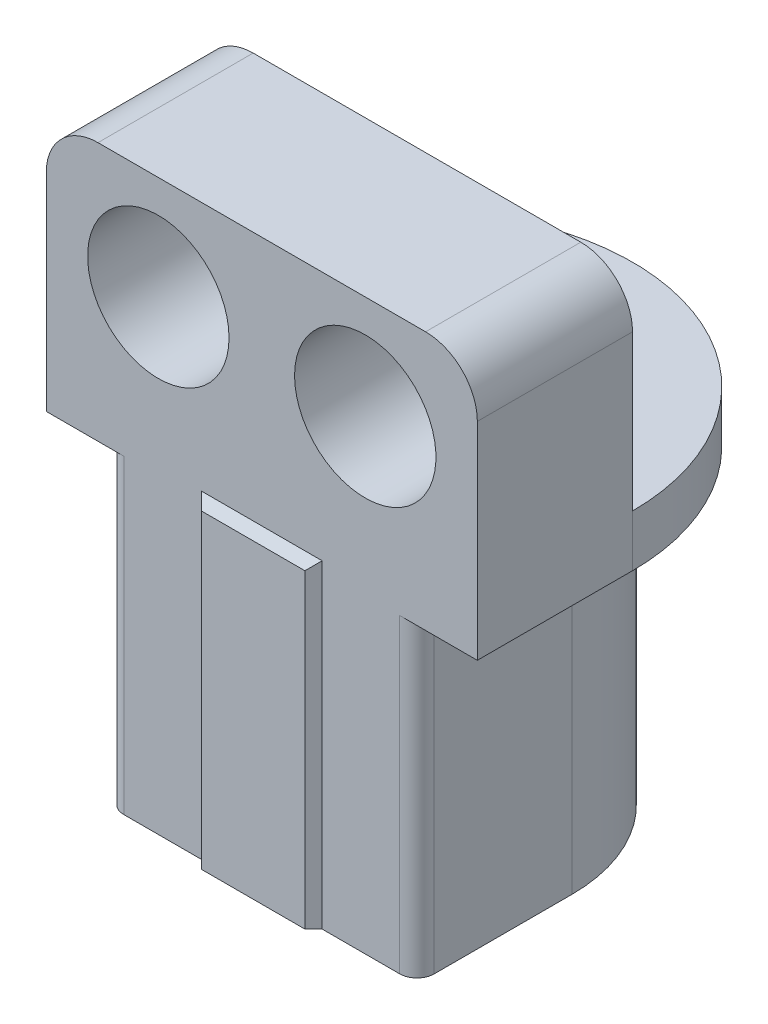
SolidWorks part; units mm, degrees
ref_plane "正面" through (0, 0, 0) normal (0, 0, 1) x (1, 0, 0)
ref_plane "平面" through (0, 0, 0) normal (0, 1, 0) x (1, 0, 0)
ref_plane "右側面" through (0, 0, 0) normal (1, 0, 0) x (0, 0, -1)
sketch "ｽｹｯﾁ1" plane through (0, 0, 0) normal (0, 1, 0) x (1, 0, 0)
  line L0 (-9, 0) -> (-9, -9)
  line L1 (-9, -9) -> (9, -9)
  line L2 (9, -9) -> (9, 0)
  arc A0 (9, 0) -> (-9, 0) centre (0, 0) ccw
  circle A1 centre (0, 0) radius 7.6
  dimension "D1" = 15.2
  dimension "D2" = 18
extrude "ﾎﾞｽ - 押し出し1" add sketch "ｽｹｯﾁ1" along normal blind 5
sketch "ｽｹｯﾁ2" plane through (0, 5, 0) normal (0, 1, 0) x (1, 0, 0)
  line L0 (9, -9) -> (9, 0) construction
  line L1 (-9, -9) -> (9, -9)
  line L2 (-9, -9) -> (-9, -4)
  line L3 (-9, -4) -> (9, -4)
  line L4 (9, -9) -> (9, -4)
  dimension "D1" = 5
extrude "ﾎﾞｽ - 押し出し2" add sketch "ｽｹｯﾁ2" along normal blind 15
sketch "ｽｹｯﾁ4" plane through (0, 5, 0) normal (0, 1, 0) x (1, 0, 0)
  line L2 (-12.5, 0) -> (-12.5, -9)
  line L3 (-12.5, -9) -> (12.5, -9)
  line L4 (12.5, -9) -> (12.5, 0)
  line L5 (-9, -9) -> (9, -9) construction
  arc A0 (12.5, 0) -> (-12.5, 0) centre (0, 0) ccw
  dimension "D1" = 25
extrude "ﾎﾞｽ - 押し出し3" add sketch "ｽｹｯﾁ4" along normal blind 3
sketch "ｽｹｯﾁ5" plane through (0, 8, 0) normal (0, 1, 0) x (1, 0, 0)
  line L1 (-9, -4) -> (-12.5, -4)
  line L2 (-9, -4) -> (-9, -9)
  line L3 (-9, -9) -> (-12.5, -9)
  line L4 (-12.5, -4) -> (-12.5, -9)
  line L5 (9, -4) -> (12.5, -4)
  line L6 (9, -4) -> (9, -9)
  line L7 (9, -9) -> (12.5, -9)
  line L8 (12.5, -4) -> (12.5, -9)
extrude "ﾎﾞｽ - 押し出し4" add sketch "ｽｹｯﾁ5" along normal up to surface (12 mm away) up to face at (0, 20, 6.5)
sketch "ｽｹｯﾁ3" plane through (0, 0, 9) normal (0, 0, 1) x (1, 0, 0)
  line L0 (-9, 14) -> (9, 14) construction
  line L3 (0, 20) -> (0, 5) construction
  line L4 (-12.5, 20) -> (12.5, 20) construction
  line L5 (-9, 5) -> (9, 5) construction
  line L6 (-9, 5) -> (-9, 0) construction
  line L7 (9, 5) -> (9, 0) construction
  line L8 (-12.5, 20) -> (12.5, 20) construction
  circle A0 centre (-6, 14) radius 4.1
  circle A1 centre (6, 14) radius 4.1
  dimension "D1" = 8.2
  dimension "D2" = 12
  dimension "D3" = 6
extrude "ｶｯﾄ - 押し出し1" cut sketch "ｽｹｯﾁ3" against normal through all
fillet "ﾌｨﾚｯﾄ4" radius 1 2 edges at (-9, 2.5, 9) (9, 2.5, 9)
sketch "ｽｹｯﾁ6" plane through (0, 0, 4) normal (0, 0, -1) x (-1, 0, 0)
  line L4 (12.5, 20) -> (-12.5, 20)
  line L5 (-12.5, 20) -> (-12.5, 8)
  line L6 (-12.5, 8) -> (12.5, 8)
  line L7 (12.5, 8) -> (12.5, 20)
  line L8 (12.5, 20) -> (-12.5, 20)
  line L9 (-12.5, 20) -> (-12.5, 8)
  line L10 (-12.5, 8) -> (12.5, 8)
  line L11 (12.5, 8) -> (12.5, 20)
  circle A1 centre (-6, 14) radius 4.1
  circle A2 centre (-6, 14) radius 4.1
  circle A3 centre (6, 14) radius 4.1
  circle A4 centre (6, 14) radius 4.1
  dimension "D1" = 0
  dimension "D2" = 0
  dimension "D3" = 0
extrude "ﾎﾞｽ - 押し出し5" add sketch "ｽｹｯﾁ6" along normal up to vertex (4 mm away) up to point (12.5, 8, 0)
fillet "ﾌｨﾚｯﾄ5" radius 3 2 edges at (12.5, 20, 4.5) (-12.5, 20, 4.5)
sketch "ｽｹｯﾁ7" plane through (0, 0, 0) normal (0, -1, 0) x (1, 0, 0)
  line L3 (8, 9) -> (-8, 9)
  line L4 (-9, 8) -> (-9, 0)
  line L5 (9, 0) -> (9, 8)
  line L6 (8, 9) -> (-8, 9)
  line L7 (-9, 8) -> (-9, 0)
  line L8 (9, 0) -> (9, 8)
  circle A0 centre (0, 0) radius 8.4
  arc A4 (-8, 9) -> (-9, 8) centre (-8, 8) ccw
  arc A5 (-9, 0) -> (9, 0) centre (0, 0) ccw
  arc A6 (9, 8) -> (8, 9) centre (8, 8) ccw
  arc A7 (-8, 9) -> (-9, 8) centre (-8, 8) ccw
  arc A8 (-9, 0) -> (9, 0) centre (0, 0) ccw
  arc A9 (9, 8) -> (8, 9) centre (8, 8) ccw
  dimension "D1" = 16.8
  dimension "D2" = 0
extrude "ﾎﾞｽ - 押し出し6" add sketch "ｽｹｯﾁ7" along normal blind 13
sketch "ｽｹｯﾁ8" plane through (0, 0, 9) normal (0, 0, 1) x (1, 0, 0)
  line L0 (8, -13) -> (-8, -13) construction
  line L1 (-3, 5) -> (3, 5)
  line L2 (-3, 5) -> (-3, -13)
  line L3 (-3, -13) -> (3, -13)
  line L4 (3, 5) -> (3, -13)
  line L5 (-3, 5) -> (3, -13) construction
  line L6 (-3, -13) -> (3, 5) construction
  line L7 (8, 5) -> (12.5, 5) construction
  line L8 (0, 0) -> (0, 5) construction
  point P0 (0, -4)
  point P12 (-3.518, -4)
  dimension "D1" = 6
extrude "ﾎﾞｽ - 押し出し7" add sketch "ｽｹｯﾁ8" along normal blind 0.5
chamfer "面取り1" distance 0.5 angle 45 3 edges at (-3, -4, 9) (0, 5, 9) (3, -4, 9)
